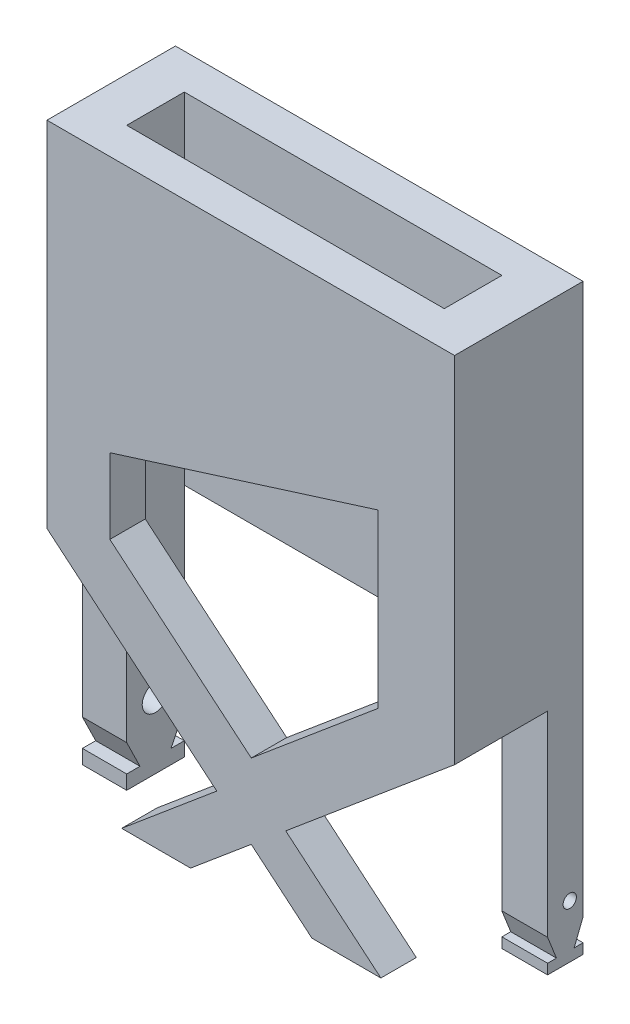
SolidWorks part; units mm, degrees
ref_plane "Front Plane" through (0, 0, 0) normal (0, 0, 1) x (1, 0, 0)
ref_plane "Top Plane" through (0, 0, 0) normal (0, 1, 0) x (1, 0, 0)
ref_plane "Right Plane" through (0, 0, 0) normal (1, 0, 0) x (0, 0, -1)
sketch "Sketch1" plane through (0, 0, 0) normal (0, 0, 1) x (1, 0, 0)
  line L0 (3.2144, 12.5583) -> (12.4144, 12.5583) construction
  line L10 (4.7926, 4.5583) -> (10.7514, -0.4417) construction
  line L11 (3.2144, 12.5583) -> (12.4144, 12.5583)
  line L12 (3.2144, 12.5583) -> (3.2144, 4.5771)
  line L14 (12.4144, 12.5583) -> (12.4144, 4.5583)
  line L15 (10.7514, -0.4417) -> (9.1957, -0.4417)
  line L16 (9.1957, -0.4417) -> (3.2144, 4.5771) construction
  line L18 (4.7926, 4.5583) -> (10.8587, 4.5583) construction
  line L19 (10.8587, 4.5583) -> (4.9, -0.4417) construction
  line L20 (4.9, -0.4417) -> (6.4557, -0.4417)
  line L21 (6.4557, -0.4417) -> (12.4144, 4.5583) construction
  line L26 (3.2144, 4.5771) -> (7.0478, 1.3605)
  line L27 (7.0478, 1.3605) -> (4.9, -0.4417)
  line L28 (12.4144, 4.5583) -> (8.6035, 1.3605)
  line L29 (8.6035, 1.3605) -> (10.7514, -0.4417)
  line L30 (6.4557, -0.4417) -> (7.8257, 0.7078)
  line L31 (7.8257, 0.7078) -> (9.1957, -0.4417)
  dimension "D1" = 8
  dimension "D2" = 13
  dimension "D3" = 9.2
  dimension "D4" = 140
  dimension "D5" = 140
  dimension "D6" = 1
  dimension "D7" = 1
extrude "Boss-Extrude1" add sketch "Sketch1" along normal blind 0.8
sketch "Sketch5" plane through (0, 0, 0) normal (0, 0, -1) x (-1, 0, 0)
  line L0 (-3.2144, 12.5583) -> (-3.2144, 4.5771) construction
  line L1 (-3.2144, 12.5583) -> (-4.2144, 12.5583)
  line L2 (-3.2144, 12.5583) -> (-3.2144, -0.4417)
  line L3 (-3.2144, -0.4417) -> (-4.2144, -0.4417)
  line L4 (-4.2144, 12.5583) -> (-4.2144, -0.4417)
  line L5 (-12.4144, 12.5583) -> (-3.2144, 12.5583) construction
  line L6 (-4.9, -0.4417) -> (-6.4557, -0.4417) construction
  line L8 (-12.4144, 12.5583) -> (-11.3826, 12.5583)
  line L9 (-12.4144, 12.5583) -> (-12.4144, 4.5583)
  line L10 (-12.4144, 4.5583) -> (-11.3826, 4.5583)
  line L11 (-11.3826, 12.5583) -> (-11.3826, 4.5583)
extrude "Boss-Extrude2" add sketch "Sketch5" along normal blind 1.3
sketch "Sketch8" plane through (0, 0, -1.3) normal (0, 0, -1) x (-1, 0, 0)
  line L1 (-12.4144, 12.5583) -> (-3.2144, 12.5583)
  line L4 (-3.2144, 12.5583) -> (-3.2144, 4.8729)
  line L5 (-3.2144, 4.8729) -> (-11.3826, 4.8729)
  line L7 (-11.3826, 4.8729) -> (-11.3826, -0.6003)
  line L8 (-11.3826, -0.6003) -> (-12.4144, -0.6003)
  line L10 (-12.4144, -0.6003) -> (-12.4144, 12.5583)
  line L14 (-3.2144, -0.4417) -> (-3.2144, 12.5583) construction
  line L15 (-11.3826, 12.5583) -> (-12.4144, 12.5583) construction
  line L16 (-12.4144, 12.5583) -> (-12.4144, 4.5583) construction
  line L17 (-11.3826, 4.5583) -> (-11.3826, 12.5583) construction
  point P4 (0, 0)
  point P8 (0, 0)
  point P10 (0, 0)
  point P11 (0, 0)
  point P13 (0, 0)
  point P14 (0, 0)
  point P15 (-13.3086, 12.2436)
extrude "Boss-Extrude3" add sketch "Sketch8" along normal blind 0.8
hole_wizard "M3 Tapped Hole1" positions "Sketch11" profile "Sketch10" tap size "M3" standard "ISO" end condition up to next
sketch "Sketch11" plane through (0, 0, -1.3) normal (0, 0, -1) x (-1, 0, 0)
  line L0 (-3.2144, -0.4417) -> (-3.2144, 4.8729) construction
  point P0 (-7.8144, 8.6497)
  dimension "D1" = 4.6
sketch "Sketch10" plane through (7.8144, 8.6497, -1.3) normal (1, 0, 0) x (0, -1, 0)
  line L0 (0, 0) -> (0, 0.8)
  line L1 (0, 0.8) -> (1.25, 0.8)
  line L2 (1.25, 0.8) -> (1.25, 0)
  line L5 (1.25, 0) -> (0, 0)
  line L11 (0, -6.35) -> (0, 107.95) construction
  dimension "Thread Major Dia." = 2.5
  dimension "Thru Tap Drill Depth" = 0.8
thread "Thread2" pitch 0.5 method cut profile "Thread Profile4" start angle 0, offset 0, length 0, pitch 0.5, diameter 2.5
ref_plane "Plane4" through (9.0644, 8.6497, -2.1) normal (0, -1, 0) x (1, 0, 0)
sketch "Thread Profile4" plane through (9.0644, 8.6497, -2.1) normal (0, -1, 0) x (1, 0, 0)
  line L0 (0, 0) -> (0, 0.5) construction
  line L1 (0, 0) -> (0.2706, 0.1562)
  line L2 (0.2706, 0.1562) -> (0.2706, 0.2187)
  line L3 (0.2706, 0.2187) -> (0, 0.375)
  line L4 (0.2706, 0.1875) -> (0, 0.1875) construction
  line L11 (0, 0) -> (0, 0.375)
  point P2 (0, 0)
  dimension "Pitch" = 0.5
  dimension "Profile_Angle" = 60
  dimension "Profile_Land" = 0.0625
  dimension "Profile_Height" = 0.2706
sketch "Sketch12" plane through (3.2144, 0, 0) normal (-1, 0, 0) x (0, 0, 1)
  line L0 (-1.3, 0.4912) -> (-1, -0.1217)
  line L1 (-1, -0.1217) -> (-1.3, -0.1217)
  line L2 (-1.3, -0.1217) -> (-1.3, 0.4912)
  line L3 (-1.3, -0.4417) -> (-1.3, 4.8729) construction
  line L4 (0, 0.4912) -> (-0.3, -0.1217)
  line L5 (-0.3, -0.1217) -> (0, -0.1217)
  line L6 (0, -0.1217) -> (0, 0.4912)
  line L7 (0, -0.4417) -> (0, 4.5771) construction
  circle A0 centre (-0.65, 1.0552) radius 0.3
  point P2 (-1.1541, 1.2628)
  point P4 (-0.7226, 1.2475)
  point P6 (-0.6411, 1.0755)
  point P7 (-0.719, 1.0586)
  point P14 (-0.6648, 1.0552)
  dimension "D2" = 0.65
  dimension "D1" = 0.7
extrude "Cut-Extrude1" cut sketch "Sketch12" against normal up to next
sketch "Sketch13" plane through (0, 0, 0.8) normal (0, 0, 1) x (1, 0, 0)
  line L3 (4.6342, 6.768) -> (4.6342, 5.0733)
  line L8 (4.6342, 5.0733) -> (7.8257, 2.3953)
  line L9 (7.8257, 2.3953) -> (10.6871, 4.7963)
  line L10 (10.6871, 4.7963) -> (10.6871, 8.6746)
  line L11 (10.6871, 8.6746) -> (4.6342, 6.768)
  line L12 (8.6035, 1.3605) -> (12.4144, 4.5583) construction
  line L13 (3.2144, 4.5771) -> (7.0478, 1.3605) construction
  point P0 (4.6342, 6.768)
  point P6 (0, 0)
extrude "Cut-Extrude2" cut sketch "Sketch13" against normal up to next
sketch "Sketch14" plane through (12.4144, 0, 0) normal (1, 0, 0) x (0, 0, -1)
  line L0 (1.3, 0.136) -> (1.5, -0.3715)
  line L1 (1.5, -0.3715) -> (1.3, -0.3715)
  line L2 (1.3, -0.3715) -> (1.3, 0.136)
  line L3 (1.3, 4.5583) -> (1.3, -0.6003) construction
  line L4 (2.1, 0.136) -> (1.9, -0.3715)
  line L5 (1.9, -0.3715) -> (2.1, -0.3715)
  line L6 (2.1, -0.3715) -> (2.1, 0.136)
  line L7 (2.1, 12.5583) -> (2.1, -0.6003) construction
  circle A0 centre (1.8, 0.5989) radius 0.15
  point P6 (1.8477, 1.081)
  point P13 (1.8, 0.5989)
  point P15 (0, 0)
  dimension "D2" = 0.5
  dimension "D1" = 0.4
extrude "Cut-Extrude3" cut sketch "Sketch14" against normal up to next
